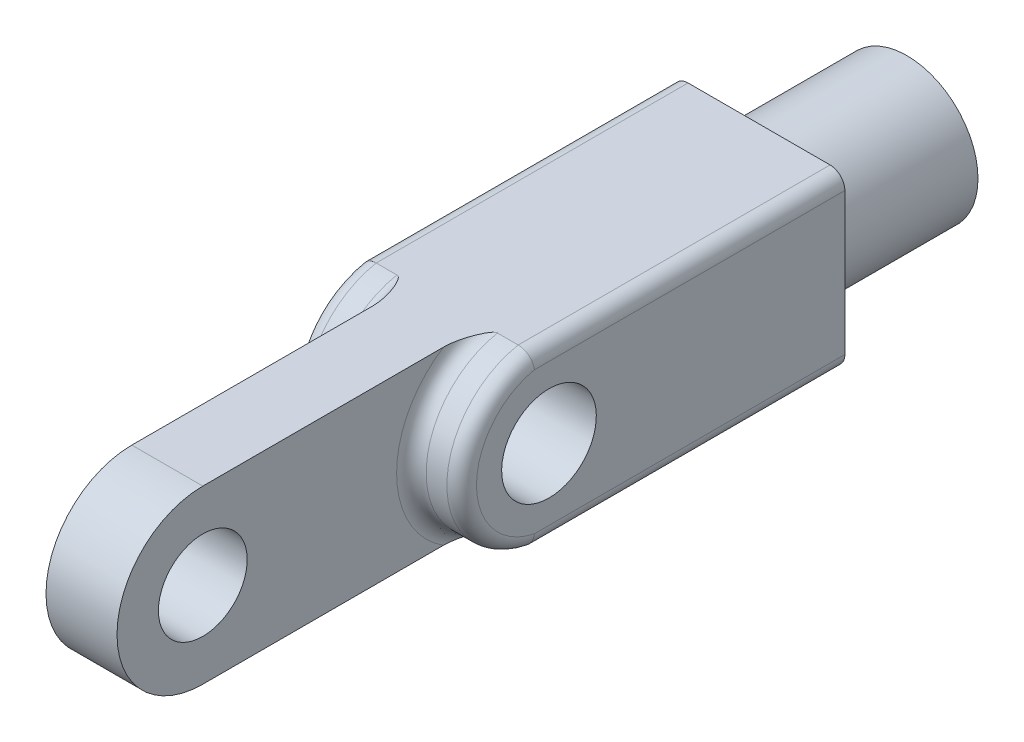
SolidWorks part; units mm, degrees
ref_plane "前视基准面" through (0, 0, 0) normal (0, 0, 1) x (1, 0, 0)
ref_plane "上视基准面" through (0, 0, 0) normal (0, 1, 0) x (1, 0, 0)
ref_plane "右视基准面" through (0, 0, 0) normal (1, 0, 0) x (0, 0, -1)
sketch "Sketch1" plane through (0, 0, 0) normal (0, 0, 1) x (1, 0, 0)
  circle A0 centre (0, 0) radius 2.4
  dimension "D1" = 4.8
extrude "Boss-Extrude1" add sketch "Sketch1" along normal blind 5
sketch "Sketch2" plane through (0, 0, 5) normal (0, 0, 1) x (1, 0, 0)
  line L1 (-2.9, 2.9) -> (-2.9, -2.9)
  line L2 (-2.9, -2.9) -> (2.9, -2.9)
  line L3 (2.9, -2.9) -> (2.9, 2.9)
  line L4 (2.9, 2.9) -> (-2.9, 2.9)
  circle A1 centre (0, 0) radius 2.9 construction
  dimension "D1" = 5.8
extrude "Boss-Extrude2" add sketch "Sketch2" along normal blind 28
sketch "Sketch3" plane through (-2.9, 0, 0) normal (-1, 0, 0) x (0, 0, 1)
  circle A0 centre (15, 0) radius 1.6
  dimension "D1" = 3.2
  dimension "D2" = 15
extrude "Cut-Extrude1" cut sketch "Sketch3" against normal blind 10
sketch "Sketch4" plane through (0, 0, 33) normal (0, 0, 1) x (1, 0, 0)
  line L0 (0, 4.3886) -> (0, -4.4033) construction
  line L1 (-1.2, 2.9) -> (-1.2, -2.9)
  line L2 (2.9, 2.9) -> (-2.9, 2.9) construction
  line L5 (1.2, 2.9) -> (1.2, -2.9)
  line L6 (-2.9, -2.9) -> (2.9, -2.9) construction
  line L7 (1.2, 2.9) -> (3.6514, 2.9)
  line L8 (3.6514, 2.9) -> (3.6514, -2.9)
  line L9 (3.6514, -2.9) -> (1.2, -2.9)
  line L10 (-3.6514, -2.9) -> (-1.2, -2.9)
  line L11 (-3.6514, 2.9) -> (-3.6514, -2.9)
  line L12 (-1.2, 2.9) -> (-3.6514, 2.9)
  point P10 (0, 2.9)
  point P11 (0, -3.641)
  dimension "D1" = 2.4
extrude "Cut-Extrude2" cut sketch "Sketch4" against normal blind 15
sketch "Sketch5" plane through (-1.2, 0, 0) normal (-1, 0, 0) x (0, 0, 1)
  line L0 (33, -2.9) -> (33, 2.9) construction
  line L1 (18, 2.9) -> (33, 2.9) construction
  line L2 (18, -2.9) -> (33, -2.9) construction
  line L3 (25, 2.9) -> (35, 2.9)
  line L4 (35, 2.9) -> (35, -2.9)
  line L5 (35, -2.9) -> (25, -2.9)
  circle A0 centre (25, 0) radius 1.5
  arc A1 (25, 2.9) -> (25, -2.9) centre (25, 0) cw
  dimension "D1" = 3
  dimension "D3" = 2.9
  dimension "D2" = 8
  dimension "D4" = 10
extrude "Cut-Extrude3" cut sketch "Sketch5" against normal blind 6
sketch "Sketch6" plane through (-2.9, 0, 0) normal (-1, 0, 0) x (0, 0, 1)
  line L0 (18, 2.9) -> (5, 2.9) construction
  line L1 (18, -2.9) -> (5, -2.9) construction
  line L3 (15.5408, 2.9) -> (18, 2.9)
  line L4 (18, 2.9) -> (18, -2.9)
  line L5 (18, -2.9) -> (15.5408, -2.9)
  arc A0 (15.5408, 2.9) -> (15.5408, -2.9) centre (15, 0) cw
  dimension "D1" = 2.95
extrude "Cut-Extrude4" cut sketch "Sketch6" against normal up to surface (1.7 mm away) up to face at (-1.2, -1.5, 25)
sketch "Sketch7" plane through (2.9, 0, 0) normal (1, 0, 0) x (0, 0, -1)
  line L3 (-15.5408, 2.9) -> (-18, 2.9)
  line L4 (-18, 2.9) -> (-18, -2.9)
  line L5 (-18, -2.9) -> (-15.5408, -2.9)
  line L6 (-15.5408, 2.9) -> (-18, 2.9)
  line L7 (-18, 2.9) -> (-18, -2.9)
  line L8 (-18, -2.9) -> (-15.5408, -2.9)
  arc A1 (-15.5408, 2.9) -> (-15.5408, -2.9) centre (-15, 0) ccw
  arc A2 (-15.5408, 2.9) -> (-15.5408, -2.9) centre (-15, 0) ccw
  dimension "D1" = 0
extrude "Cut-Extrude5" cut sketch "Sketch7" against normal up to surface (1.7 mm away) up to face at (1.2, 0, 26.5)
fillet "Fillet1" radius 0.5 8 edges at (2.9, 2.9, 10.2704) (-2.9, 2.9, 10.2704) (-2.9, -2.9, 10.2704) (2.9, -2.9, 10.2704) (2.9, 0, 17.95) (-2.9, 0, 17.95) (-1.2, 0, 17.95) (1.2, 0, 17.95)
